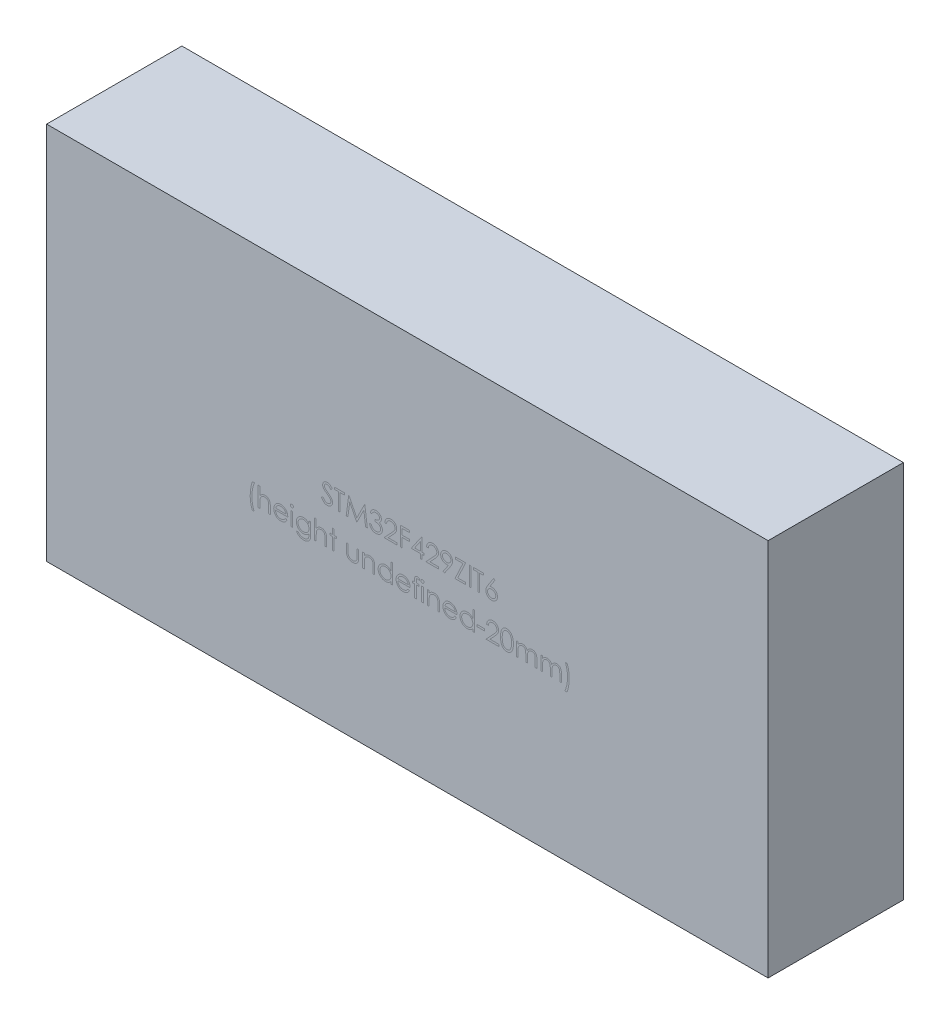
SolidWorks part; units mm, degrees
ref_plane "정면" through (0, 0, 0) normal (0, 0, 1) x (1, 0, 0)
ref_plane "윗면" through (0, 0, 0) normal (0, 1, 0) x (1, 0, 0)
ref_plane "우측면" through (0, 0, 0) normal (1, 0, 0) x (0, 0, -1)
sketch "스케치1" plane through (0, 0, 0) normal (0, 0, 1) x (1, 0, 0)
  line L1 (-66.67, 35) -> (66.67, 35)
  line L2 (-66.67, 35) -> (-66.67, -35)
  line L3 (-66.67, -35) -> (66.67, -35)
  line L4 (66.67, 35) -> (66.67, -35)
  line L5 (-66.67, 35) -> (66.67, -35) construction
  line L6 (-66.67, -35) -> (66.67, 35) construction
  point P0 (0, 0)
  dimension "D1" = 133.34
  dimension "D2" = 70
extrude "보스-돌출1" add sketch "스케치1" along normal blind 25
ref_plane "평면1" through (0, 0, 35) normal (0, 0, 1) x (1, 0, 0)
sketch "스케치3" plane through (0, 0, 35) normal (0, 0, 1) x (1, 0, 0)
  line L0 (-66.67, 0) -> (67.5821, 0) construction
  line L1 (-66.67, 35) -> (-66.67, -35) construction
  text T0 "STM32F429ZIT6\r\n(height undefined-20mm)"
wrap "곡면 포장1" sketch "스케치3" wrap type scribe source sketch "스케치3" face at (0, 0, 25)
